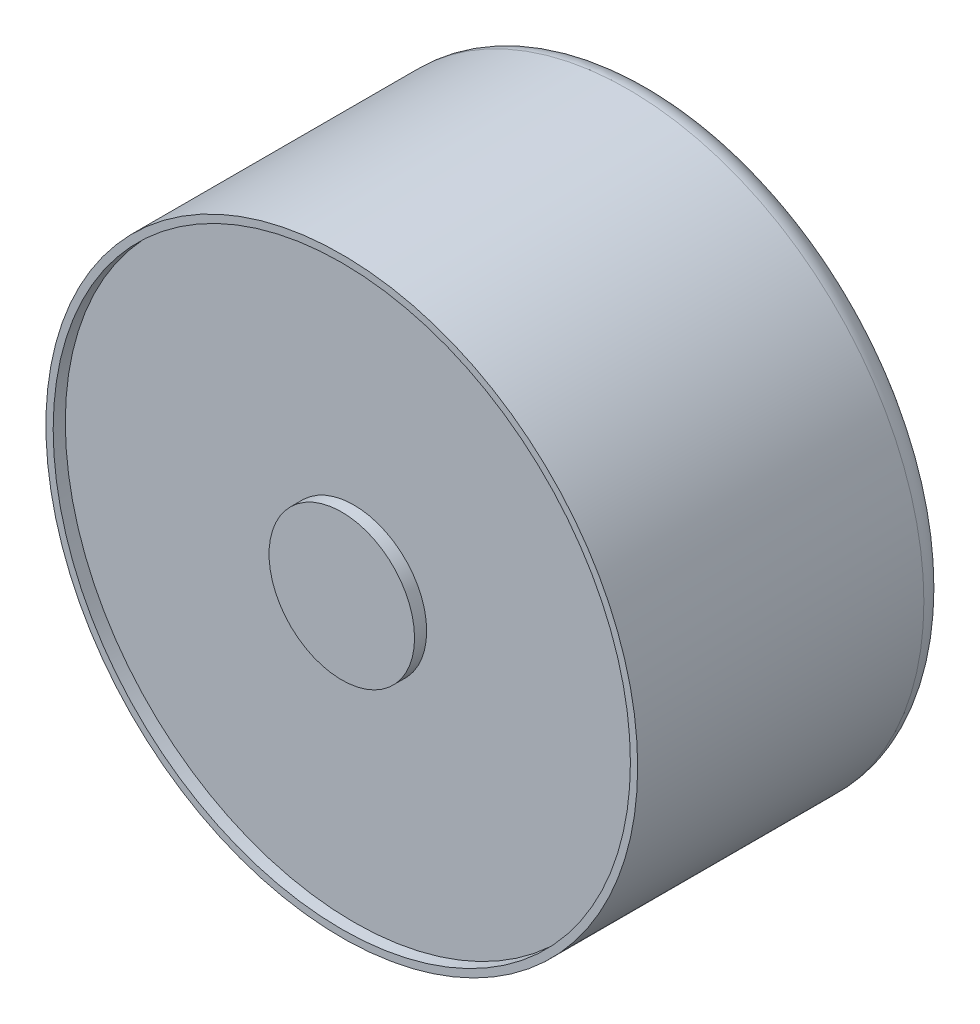
SolidWorks part; units mm, degrees
ref_plane "Front Plane" through (0, 0, 0) normal (0, 0, 1) x (1, 0, 0)
ref_plane "Top Plane" through (0, 0, 0) normal (0, 1, 0) x (1, 0, 0)
ref_plane "Right Plane" through (0, 0, 0) normal (1, 0, 0) x (0, 0, -1)
sketch "Sketch1" plane through (0, 0, 0) normal (0, 1, 0) x (1, 0, 0)
  line L0 (0, 0) -> (0, 17.0776) construction
  line L1 (0, 0) -> (3, 0)
  line L2 (3, 0) -> (3, 0.5)
  line L3 (3, 0.5) -> (11.9, 0.5)
  line L4 (11.9, 0.5) -> (11.9, 0)
  line L5 (11.9, 0) -> (12.2, 0)
  line L6 (12.2, 0) -> (12.2, 11.8)
  line L7 (11.2, 12.8) -> (3, 12.8)
  line L8 (3, 12.8) -> (3, 13.3)
  line L9 (3, 13.3) -> (0, 13.3)
  line L10 (0, 13.3) -> (0, 0)
  arc A0 (12.2, 11.8) -> (11.2, 12.8) centre (11.2, 11.8) ccw
  point P14 (12.2, 12.8)
  dimension "D7" = 1
  dimension "D1" = 12.8
  dimension "D2" = 12.2
  dimension "D3" = 0.5
  dimension "D4" = 3
  dimension "D5" = 0.3
  dimension "D6" = 0.5
revolve "Revolve1" add sketch "Sketch1" angle 360 about L0
sketch "Sketch2" plane through (0, 0, -13.3) normal (0, 0, -1) x (-1, 0, 0)
  circle A0 centre (0, 0) radius 1
  dimension "D1" = 2
extrude "Boss-Extrude1" add sketch "Sketch2" along normal blind 6
hole_wizard "M1.6 Clearance Hole1" positions "Sketch3" profile "Sketch4" hole size "M1.6" standard "ANSI Metric"
sketch "Sketch3" plane through (0, 0, -12.8) normal (0, 0, -1) x (-1, 0, 0)
  point P0 (0, 8.25)
  dimension "D1" = 8.25
sketch "Sketch4" plane through (0, 8.25, -12.8) normal (1, 0, 0) x (0, 1, 0)
  line L0 (0, 0) -> (0, 3.6009)
  line L1 (0, 3.6009) -> (1, 3)
  line L2 (1, 3) -> (1, 0)
  line L5 (1, 0) -> (0, 0)
  line L10 (0, 3.6009) -> (-1, 3) construction
  line L11 (0, -6.35) -> (0, 107.95) construction
  dimension "Hole Dia." = 2
  dimension "Hole Depth" = 3
  dimension "Drill Angle" = 118
pattern_circular "CirPattern1" count 6 over 360 about axis through (0, 0, -12.8) along (0, 0, 1) of "M1.6 Clearance Hole1"
